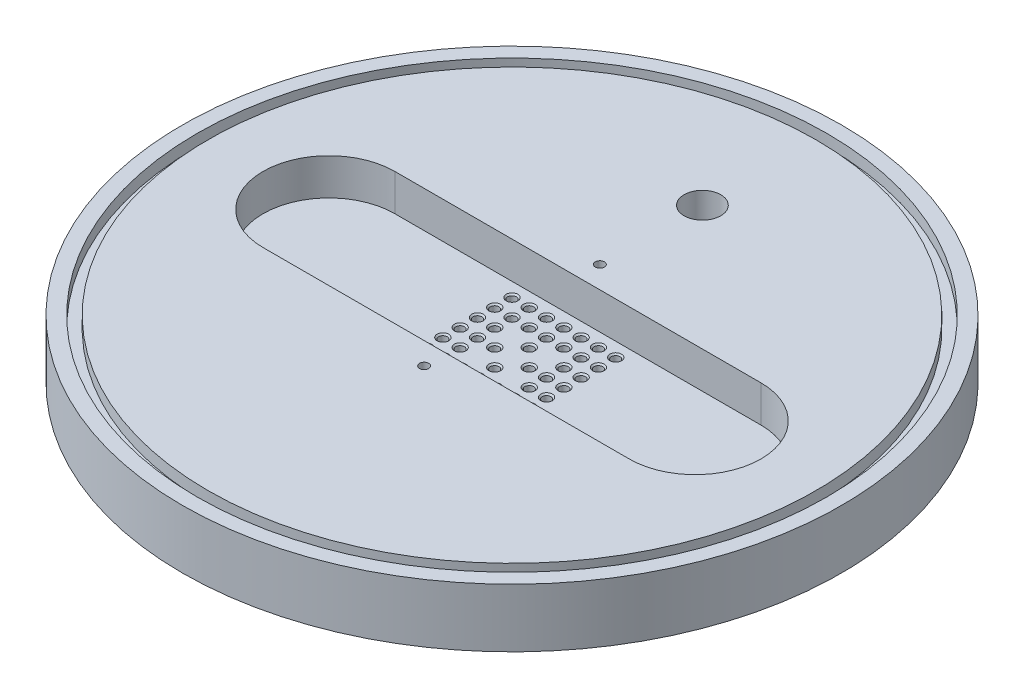
SolidWorks part; units mm, degrees
ref_plane "Front Plane" through (0, 0, 0) normal (0, 0, 1) x (1, 0, 0)
ref_plane "Top Plane" through (0, 0, 0) normal (0, 1, 0) x (1, 0, 0)
ref_plane "Right Plane" through (0, 0, 0) normal (1, 0, 0) x (0, 0, -1)
ref_axis "Axial" through (0, 0.508, 0) along (0, -1, 0)
ref_plane "Bottom Plane" through (0, -10.16, 0) normal (0, 1, 0) x (1, 0, 0)
sketch "Sketch1" plane through (0, 0, 0) normal (0, 1, 0) x (1, 0, 0)
  circle A0 centre (0, 0) radius 57.15
  dimension "D1" = 114.3
extrude "Billet" add sketch "Sketch1" against normal blind 10.16
sketch "Sketch2" plane through (0, 0, 0) normal (0, 1, 0) x (1, 0, 0)
  line L0 (-71.6435, 0) -> (78.9532, 0) construction
  line L1 (-31.75, 11.43) -> (31.75, 11.43)
  line L2 (-31.75, -11.43) -> (31.75, -11.43)
  line L3 (0, 44.5081) -> (0, -98.5298) construction
  arc A4 (-31.75, 11.43) -> (-31.75, -11.43) centre (-31.75, 0) ccw
  arc A5 (31.75, -11.43) -> (31.75, 11.43) centre (31.75, 0) ccw
  dimension "D1" = 22.86
  dimension "D2" = 31.75
extrude "Kerosene Well" cut sketch "Sketch2" against normal blind 6.35
sketch "Sketch4" plane through (0, -10.16, 0) normal (0, 1, 0) x (1, 0, 0)
  line L0 (0, 37.2675) -> (0, -28.2573) construction
  line L1 (-38.2015, 0) -> (37.6086, 0) construction
  circle A0 centre (8.9916, 8.9916) radius 0.7493
  dimension "D1" = 1.4986
  dimension "D2" = 8.9916
  dimension "D3" = 8.9916
extrude "First Kerosene Outlet" cut sketch "Sketch4" along normal up to next
chamfer "Bottom Needle Chamfer" distance 0.254 angle 45 1 edges at (8.9916, -6.35, -8.2423)
pattern_linear "LPattern1" count 7 spacing 2.9972 along (0, 0, 1) count 7 spacing 2.9972 along (-1, 0, 0) skipping (2, 2), (2, 4), (3, 3), (4, 2), (4, 4) of "First Kerosene Outlet", "Bottom Needle Chamfer"
sketch "Sketch13" plane through (0, 0, 0) normal (0, 1, 0) x (1, 0, 0)
  line L0 (0, 67.9606) -> (0, -66.9336) construction
  line L1 (-21.7094, 0) -> (16.1787, 0) construction
  circle A0 centre (0, 15.24) radius 0.7937
  circle A1 centre (0, -15.24) radius 0.7937
  dimension "D1" = 1.5875
  dimension "D2" = 15.24
extrude "Dowel Holes" cut sketch "Sketch13" against normal blind 3.175
sketch "Sketch14" plane through (0, 0, 0) normal (0, 1, 0) x (1, 0, 0)
  line L0 (0, 62.0498) -> (0, -64.4455) construction
  circle A0 centre (0, 33.02) radius 3.175
  dimension "D1" = 6.35
  dimension "D2" = 33.02
extrude "Manifold Hole" cut sketch "Sketch14" against normal up to next
sketch "Sketch15" plane through (0, -10.16, 0) normal (0, 1, 0) x (1, 0, 0)
  circle A0 centre (0, 0) radius 54.61
  circle A1 centre (0, 0) radius 56.515
  dimension "D1" = 109.22
  dimension "D2" = 113.03
extrude "Chamber O Ring" cut sketch "Sketch15" along normal blind 2.032
sketch "Sketch16" plane through (0, 0, 0) normal (0, 1, 0) x (1, 0, 0)
  circle A0 centre (0, 0) radius 54.61
  circle A1 centre (0, 0) radius 52.705
  dimension "D1" = 109.22
  dimension "D2" = 105.41
extrude "Cut-Extrude4" cut sketch "Sketch16" against normal blind 2.032
